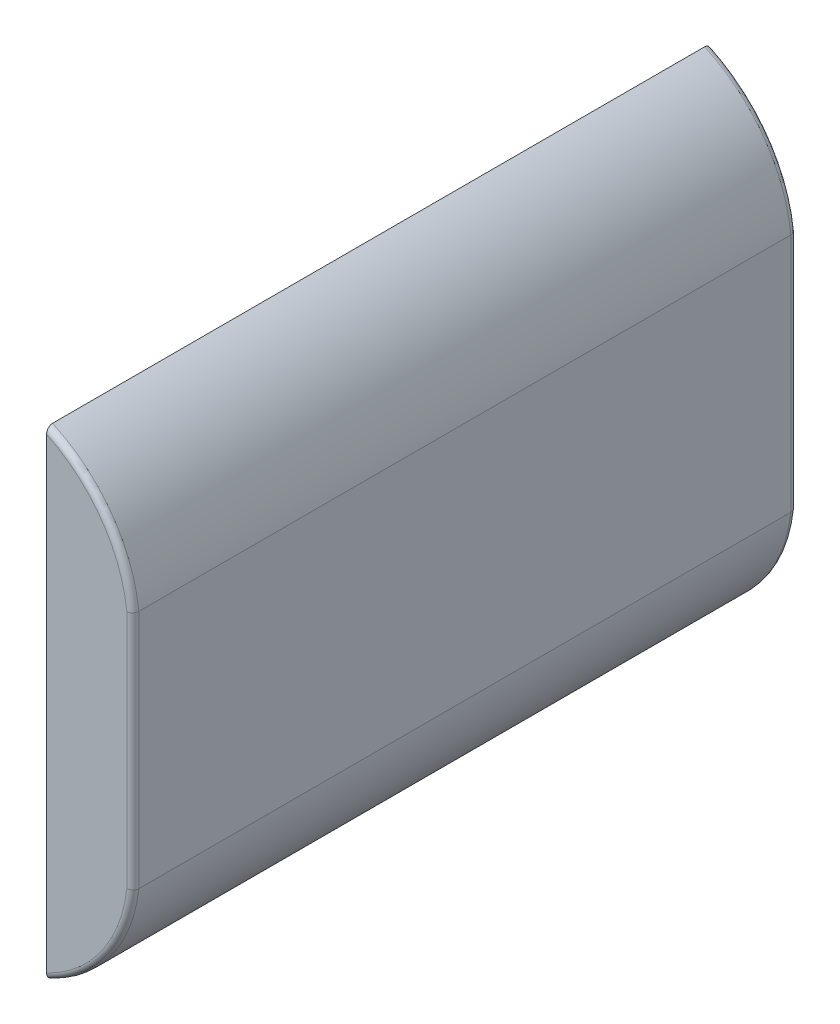
SolidWorks part; units mm, degrees
ref_plane "Front Plane" through (0, 0, 0) normal (0, 0, 1) x (1, 0, 0)
ref_plane "Top Plane" through (0, 0, 0) normal (0, 1, 0) x (1, 0, 0)
ref_plane "Right Plane" through (0, 0, 0) normal (1, 0, 0) x (0, 0, -1)
sketch "Sketch for the main shape" plane through (0, 0, 0) normal (0, 0, 1) x (1, 0, 0)
  line L0 (14.3611, 19.95) -> (14.3611, 59.95)
  line L2 (0, 0) -> (0, 79.9)
  line L5 (36.6965, 39.95) -> (-8.6243, 39.95) construction
  arc A0 (0, 79.9) -> (14.3611, 59.95) centre (-10.3617, 57.2972) cw
  arc A1 (0, 0) -> (14.3611, 19.95) centre (-10.3617, 22.6028) ccw
  point P9 (14.3611, 39.95)
  dimension "D2" = 20
  dimension "D3" = 24.8647
  dimension "D1" = 79.9
  dimension "D4" = 14.3611
extrude "Main shape" add sketch "Sketch for the main shape" along normal blind 110.6
shell "Hollow" thickness 1.8 removed face at (0, 39.95, 55.3)
fillet "Fillets" radius 1 6 edges at (9.8183, 8.0762, 110.6) (14.3611, 39.95, 110.6) (9.8183, 71.8238, 110.6) (9.8183, 71.8238, 0) (14.3611, 39.95, 0) (9.8183, 8.0762, 0)
